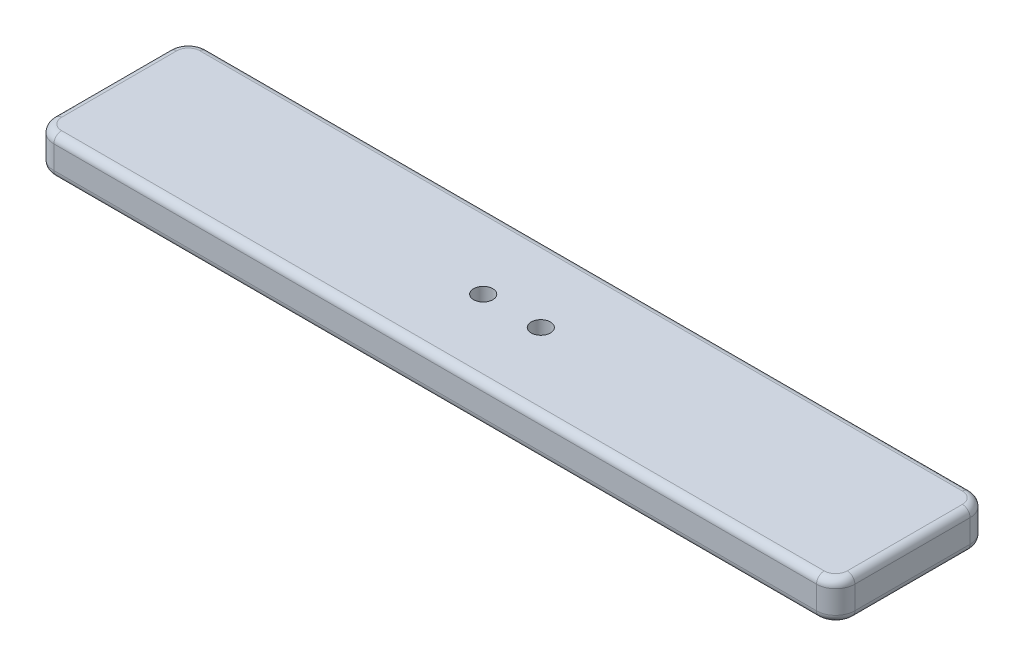
SolidWorks part; units mm, degrees
ref_plane "Front Plane" through (0, 0, 0) normal (0, 0, 1) x (1, 0, 0)
ref_plane "Top Plane" through (0, 0, 0) normal (0, 1, 0) x (1, 0, 0)
ref_plane "Right Plane" through (0, 0, 0) normal (1, 0, 0) x (0, 0, -1)
sketch "Sketch1" plane through (0, 0, 0) normal (0, 1, 0) x (1, 0, 0)
  line L0 (19.9485, 50.8) -> (284.8515, 0) construction
  line L1 (19.9485, 0) -> (284.8515, 0)
  line L2 (19.9485, 0) -> (19.9485, 50.8)
  line L3 (19.9485, 50.8) -> (284.8515, 50.8)
  line L4 (284.8515, 0) -> (284.8515, 50.8)
  line L5 (284.8515, 50.8) -> (19.9485, 0) construction
  point P5 (152.4, 25.4)
  dimension "D2" = 50.8
extrude "Boss-Extrude1" add sketch "Sketch1" along normal blind 12.7
sketch "Sketch2" plane through (0, 12.7, 0) normal (0, 1, 0) x (1, 0, 0)
  line L0 (19.9485, 50.8) -> (284.8515, 0) construction
  line L1 (284.8515, 0) -> (284.8515, 50.8) construction
  line L2 (284.8515, 50.8) -> (0, 0) construction
  line L3 (152.4, 25.4) -> (152.4, 50025.4) construction
  circle A0 centre (142.875, 25.4) radius 3.175
  circle A1 centre (161.925, 25.4) radius 3.175
  point P4 (152.4, 25.4)
  dimension "D1" = 6.35
  dimension "D2" = 9.525
fillet "Fillet1" radius 6.35 4 edges at (284.8515, 6.35, -50.8) (284.8515, 6.35, 0) (19.9485, 6.35, -50.8) (19.9485, 6.35, 0)
fillet "Fillet2" radius 2.54 16 edges at (21.8083, 0, -48.9401) (19.9485, 0, -25.4) (21.8083, 0, -1.8599) (152.4, 0, 0) (282.9917, 0, -1.8599) (284.8515, 0, -25.4) (282.9917, 0, -48.9401) (152.4, 0, -50.8) (282.9917, 12.7, -1.8599) (152.4, 12.7, 0) (21.8083, 12.7, -1.8599) (19.9485, 12.7, -25.4) (21.8083, 12.7, -48.9401) (152.4, 12.7, -50.8) (282.9917, 12.7, -48.9401) (284.8515, 12.7, -25.4)
extrude "Cut-Extrude1" cut sketch "Sketch2" against normal through all
